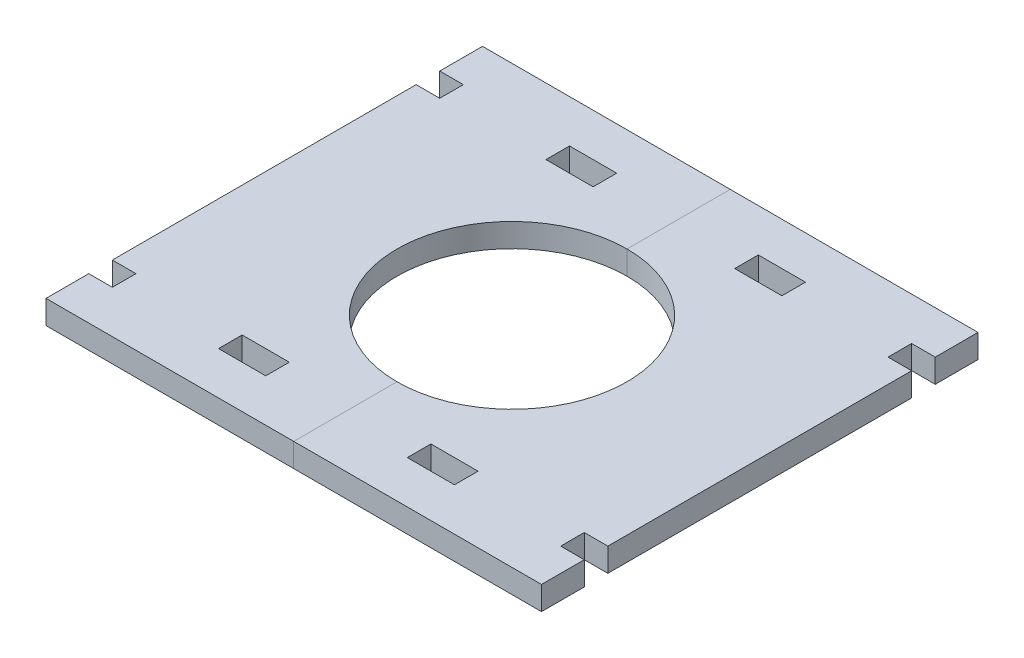
SolidWorks part; units mm, degrees
ref_plane "Front Plane" through (0, 0, 0) normal (0, 0, 1) x (1, 0, 0)
ref_plane "Top Plane" through (0, 0, 0) normal (0, 1, 0) x (1, 0, 0)
ref_plane "Right Plane" through (0, 0, 0) normal (1, 0, 0) x (0, 0, -1)
sketch "Sketch1" plane through (0, 0, 0) normal (0, 1, 0) x (1, 0, 0)
  circle A2 centre (0, 0) radius 19.5
  dimension "D1" = 39
sketch "Sketch2" plane through (0, 0, 0) normal (0, 1, 0) x (1, 0, 0)
  line L17 (-42, -37) -> (42, -37)
  line L18 (-42, -37) -> (-42, 37)
  line L19 (-42, 37) -> (42, 37)
  line L20 (42, -37) -> (42, 37)
  circle A15 centre (0, 0) radius 19.5
  circle A16 centre (0, 0) radius 19.5
  point P0 (42, 0)
  point P1 (0, 37)
  dimension "D1" = 84
  dimension "D2" = 74
extrude "Boss-Extrude1" add sketch "Sketch2" along normal blind 4 contours L17 L20 L19 L18 region at (-40.8805, 0, 0)
split "Split1" trim tools "Right Plane" bodies to split 101 resulting bodies 102 103
sketch "Sketch4" plane through (0, 4, 0) normal (0, 1, 0) x (1, 0, 0)
  line L0 (0, -18.5) -> (42, -18.5) construction
  line L2 (42, -37) -> (42, 37) construction
  line L3 (0, -18.5) -> (0, -37) construction
  line L4 (-42, -37) -> (-42, 37) construction
  line L5 (-20, -29.75) -> (-12, -29.75)
  line L6 (-20, -29.75) -> (-20, -25.75)
  line L7 (-20, -25.75) -> (-12, -25.75)
  line L8 (-12, -29.75) -> (-12, -25.75)
  line L9 (-20, -29.75) -> (-12, -25.75) construction
  line L10 (-20, -25.75) -> (-12, -29.75) construction
  line L11 (-42, -29.75) -> (-38, -29.75)
  line L12 (-42, -29.75) -> (-42, -25.75)
  line L13 (-42, -25.75) -> (-38, -25.75)
  line L14 (-38, -29.75) -> (-38, -25.75)
  line L15 (-42, -29.75) -> (-38, -25.75) construction
  line L16 (-42, -25.75) -> (-38, -29.75) construction
  line L17 (0, 0) -> (0, -37) construction
  line L33 (42, -25.75) -> (38, -29.75) construction
  line L34 (42, -29.75) -> (38, -25.75) construction
  line L35 (20, -25.75) -> (12, -29.75) construction
  line L36 (20, -29.75) -> (12, -25.75) construction
  line L45 (38, -29.75) -> (38, -25.75)
  line L46 (42, -25.75) -> (38, -25.75)
  line L47 (42, -29.75) -> (42, -25.75)
  line L48 (42, -29.75) -> (38, -29.75)
  line L49 (12, -29.75) -> (12, -25.75)
  line L50 (20, -25.75) -> (12, -25.75)
  line L51 (20, -29.75) -> (20, -25.75)
  line L52 (20, -29.75) -> (12, -29.75)
  line L53 (-2.2, 0) -> (2.2, 0) construction
  line L54 (20, 29.75) -> (12, 25.75) construction
  line L55 (20, 25.75) -> (12, 29.75) construction
  line L56 (42, 29.75) -> (38, 25.75) construction
  line L57 (42, 25.75) -> (38, 29.75) construction
  line L58 (20, 29.75) -> (12, 29.75)
  line L59 (20, 29.75) -> (20, 25.75)
  line L60 (20, 25.75) -> (12, 25.75)
  line L61 (12, 29.75) -> (12, 25.75)
  line L62 (42, 29.75) -> (38, 29.75)
  line L63 (42, 29.75) -> (42, 25.75)
  line L64 (42, 25.75) -> (38, 25.75)
  line L65 (38, 29.75) -> (38, 25.75)
  line L82 (-42, 25.75) -> (-38, 29.75) construction
  line L83 (-42, 29.75) -> (-38, 25.75) construction
  line L84 (-20, 25.75) -> (-12, 29.75) construction
  line L85 (-20, 29.75) -> (-12, 25.75) construction
  line L94 (-38, 29.75) -> (-38, 25.75)
  line L95 (-42, 25.75) -> (-38, 25.75)
  line L96 (-42, 29.75) -> (-42, 25.75)
  line L97 (-42, 29.75) -> (-38, 29.75)
  line L98 (-12, 29.75) -> (-12, 25.75)
  line L99 (-20, 25.75) -> (-12, 25.75)
  line L100 (-20, 29.75) -> (-20, 25.75)
  line L101 (-20, 29.75) -> (-12, 29.75)
  point P6 (-16, -27.75)
  point P14 (0, -27.75)
  point P15 (-40, -27.75)
  point P53 (40, -27.75)
  point P54 (16, -27.75)
  point P65 (16, 27.75)
  point P66 (40, 27.75)
  point P95 (-40, 27.75)
  point P96 (-16, 27.75)
  dimension "D1" = 4
  dimension "D2" = 8
  dimension "D3" = 20
  dimension "D4" = 4
extrude "Cut-Extrude2" cut sketch "Sketch4" against normal through all both
equation "\"m3_hole\"= 3.5"
equation "\"m3_washer\"= 7.3"
equation "\"m3_nut\"= 5.3"
equation "\"guide_width\"= 10.0"
equation "\"guide_length\"= 65.0"
equation "\"guide_tab_length\" = 10.0"
equation "\"guide_tab_width\" = 9.0"
equation "\"guide_thickness\" = 12.0"
equation "\"grinder_od\"= 52.0"
equation "\"grinder_id\"= 45.5"
equation "\"grinder_adjust_od\" = 58.0"
equation "\"funnel_width_from_adjust_ring\" = 13.0"
equation "\"drill_contact_diameter_small\" = 24.0"
equation "\"drill_contact_diameter_medium\" = 28.0"
equation "\"drill_contact_diameter_large\" = 39.0"
equation "\"drill_contact_diameter_tab\" = 31.0"
equation "\"drill_contact_ow_tab\" = 14.5"
equation "\"drill_contact_iw_tab\" = 8.7"
equation "\"drill_contact_small_height\" = 15.5"
equation "\"drill_contact_large_height\" = 34.5"
equation "\"D1@Sketch2\"=\"grinder_od\"+\"guide_thickness\"+20"
equation "\"D2@Sketch2\"=\"grinder_od\"+\"guide_thickness\"+\"guide_tab_length\""
equation "\"plywood_thickness\" = 4.0"
equation "\"plywood_peg_length\" = 40.0"
equation "\"plywood_peg_width\" = 8.0"
equation "\"D3@Sketch4\"=\"plywood_peg_length\"/2"
equation "\"D2@Sketch4\"=\"plywood_peg_width\""
equation "\"D1@Sketch4\"=\"plywood_thickness\""
equation "\"D4@Sketch4\"=\"plywood_thickness\""
equation "\"D1@Sketch1\"=\"drill_contact_diameter_large\""
